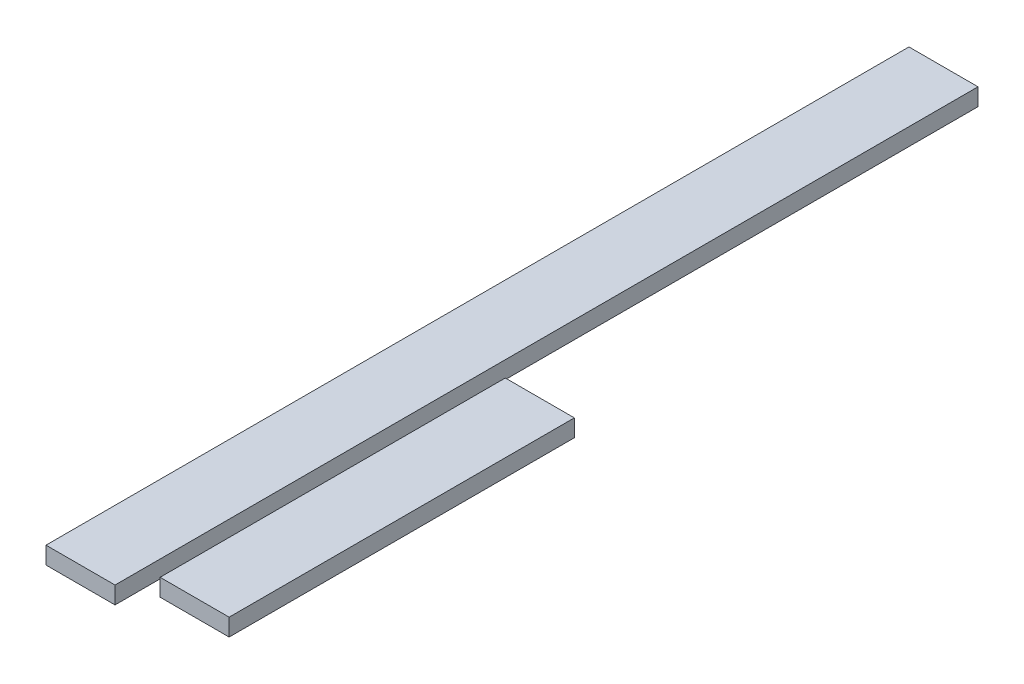
SolidWorks part; units mm, degrees
ref_plane "Front Plane" through (0, 0, 0) normal (0, 0, 1) x (1, 0, 0)
ref_plane "Top Plane" through (0, 0, 0) normal (0, 1, 0) x (1, 0, 0)
ref_plane "Right Plane" through (0, 0, 0) normal (1, 0, 0) x (0, 0, -1)
sketch "Sketch2" plane through (0, 0, 0) normal (0, 1, 0) x (1, 0, 0)
  line L1 (57.8363, 166.5718) -> (69.8363, 166.5718)
  line L2 (57.8363, 166.5718) -> (57.8363, 16.5718)
  line L3 (57.8363, 16.5718) -> (69.8363, 16.5718)
  line L4 (69.8363, 166.5718) -> (69.8363, 16.5718)
  dimension "D1" = 12
  dimension "D2" = 150
extrude "Boss-Extrude4" add sketch "Sketch2" along normal blind 3 separate body
sketch "Sketch3" plane through (0, 0, 0) normal (0, 1, 0) x (1, 0, 0)
  line L1 (93.6296, 73.2668) -> (105.6296, 73.2668)
  line L2 (93.6296, 73.2668) -> (93.6296, 13.2668)
  line L3 (93.6296, 13.2668) -> (105.6296, 13.2668)
  line L4 (105.6296, 73.2668) -> (105.6296, 13.2668)
  dimension "D1" = 12
  dimension "D2" = 60
extrude "Boss-Extrude5" add sketch "Sketch3" along normal blind 3 separate body
sketch "Sketch4" plane through (0, 3, 0) normal (0, 1, 0) x (1, 0, 0)
  line L0 (-38.3775, -12.3557) -> (21.6225, -12.3557) construction
  line L1 (21.6225, -12.3557) -> (21.6225, 137.6443) construction
  line L2 (-38.3775, 137.6443) -> (-38.3775, -12.3557) construction
  circle A0 centre (4.6225, 10.6443) radius 8
  circle A1 centre (-21.3775, 10.6443) radius 8
  circle A2 centre (4.6225, 45.6443) radius 8
  circle A3 centre (-21.3775, 45.6443) radius 8
  circle A4 centre (4.6225, 80.6443) radius 8
  circle A5 centre (-21.3775, 80.6443) radius 8
  circle A6 centre (4.6225, 115.6443) radius 8
  circle A7 centre (-21.3775, 115.6443) radius 8
  dimension "D1" = 16
  dimension "D2" = 23
  dimension "D3" = 17
  dimension "D4" = 16
  dimension "D5" = 26
  dimension "D6" = 17
  dimension "D7" = 4
extrude "Cut-Extrude1" cut sketch "Sketch4" against normal blind 3 rebuild error yes
move or copy body "Body-Move/Copy1" bodies to move or copy 106 copy no translate (-21.0375, 0, -8.3838)
